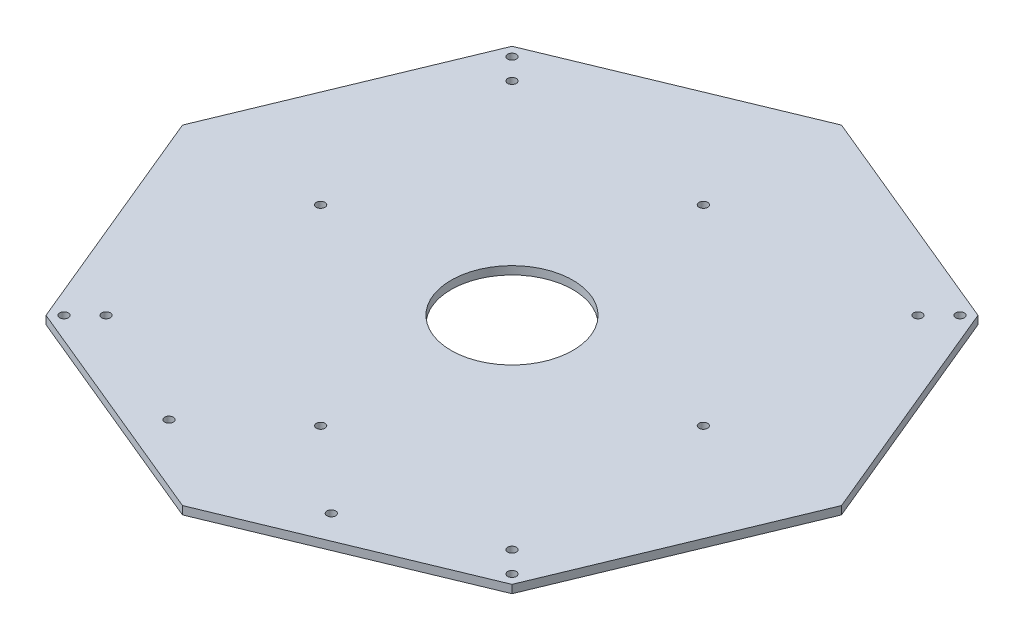
SolidWorks part; units mm, degrees
ref_plane "Front Plane" through (0, 0, 0) normal (0, 0, 1) x (1, 0, 0)
ref_plane "Top Plane" through (0, 0, 0) normal (0, 1, 0) x (1, 0, 0)
ref_plane "Right Plane" through (0, 0, 0) normal (1, 0, 0) x (0, 0, -1)
sketch "Sketch1" plane through (0, 0, 0) normal (0, 1, 0) x (1, 0, 0)
  line L0 (0, -121.7691) -> (86.1038, -86.1038)
  line L7 (0, 121.7691) -> (-86.1038, 86.1038)
  line L8 (-86.1038, 86.1038) -> (-121.7691, 0)
  line L9 (-121.7691, 0) -> (-86.1038, -86.1038)
  line L10 (-86.1038, -86.1038) -> (0, -121.7691)
  line L11 (86.1038, -86.1038) -> (121.7691, 0)
  line L12 (121.7691, 0) -> (86.1038, 86.1038)
  line L13 (86.1038, 86.1038) -> (0, 121.7691)
  circle A0 centre (0, 0) radius 112.5 construction
  dimension "D1" = 225
extrude "Boss-Extrude2" add sketch "Sketch1" along normal blind 3
sketch "Sketch3" plane through (0, 3, 0) normal (0, 1, 0) x (1, 0, 0)
  line L0 (-121.7691, 0) -> (121.7691, 0) construction
  line L1 (0, 121.7691) -> (0, -121.7691) construction
  line L2 (-75, -75) -> (0, 0) construction
  circle A0 centre (-75, -75) radius 1.6
  circle A1 centre (75, -75) radius 1.6
  circle A2 centre (75, 75) radius 1.6
  circle A3 centre (-75, 75) radius 1.6
  circle A4 centre (-70.7107, 0) radius 1.6
  circle A5 centre (0, 70.7107) radius 1.6
  circle A6 centre (70.7107, 0) radius 1.6
  circle A7 centre (0, -70.7107) radius 1.6
  point P28 (0, 0)
  dimension "D1" = 3.2
  dimension "D4" = 3.2
  dimension "D2" = 150
  dimension "D3" = 150
  dimension "D6" = 100
  dimension "D5" = 4
extrude "Cut-Extrude3" cut sketch "Sketch3" against normal through all both and the other way through all
sketch "Sketch4" plane through (0, 3, 0) normal (0, 1, 0) x (1, 0, 0)
  line L0 (0, -121.7691) -> (0, -96.7691) construction
  circle A0 centre (-30, -96.7691) radius 1.6
  circle A1 centre (30, -96.7691) radius 1.6
  dimension "D1" = 3.2
  dimension "D2" = 60
  dimension "D3" = 25
extrude "Cut-Extrude4" cut sketch "Sketch4" against normal through all both and the other way through all
sketch "Sketch5" plane through (0, 3, 0) normal (0, 1, 0) x (1, 0, 0)
  line L0 (0, 0) -> (-86.1038, -86.1038) construction
  circle A0 centre (-82.7782, -82.7782) radius 1.6
  circle A6 centre (-75, -75) radius 1.6 construction
  circle A7 centre (-82.7782, 82.7782) radius 1.6
  circle A8 centre (82.7782, 82.7782) radius 1.6
  circle A9 centre (82.7782, -82.7782) radius 1.6
  point P18 (0, 0)
  point P21 (0, 0)
  dimension "D1" = 3.2
  dimension "D2" = 4
  dimension "D3" = 11
extrude "Cut-Extrude5" cut sketch "Sketch5" against normal through all both and the other way through all
sketch "Sketch6" plane through (0, 3, 0) normal (0, 1, 0) x (1, 0, 0)
  circle A0 centre (0, 0) radius 22.5
  dimension "D1" = 45
extrude "Cut-Extrude6" cut sketch "Sketch6" against normal through all both and the other way through all
